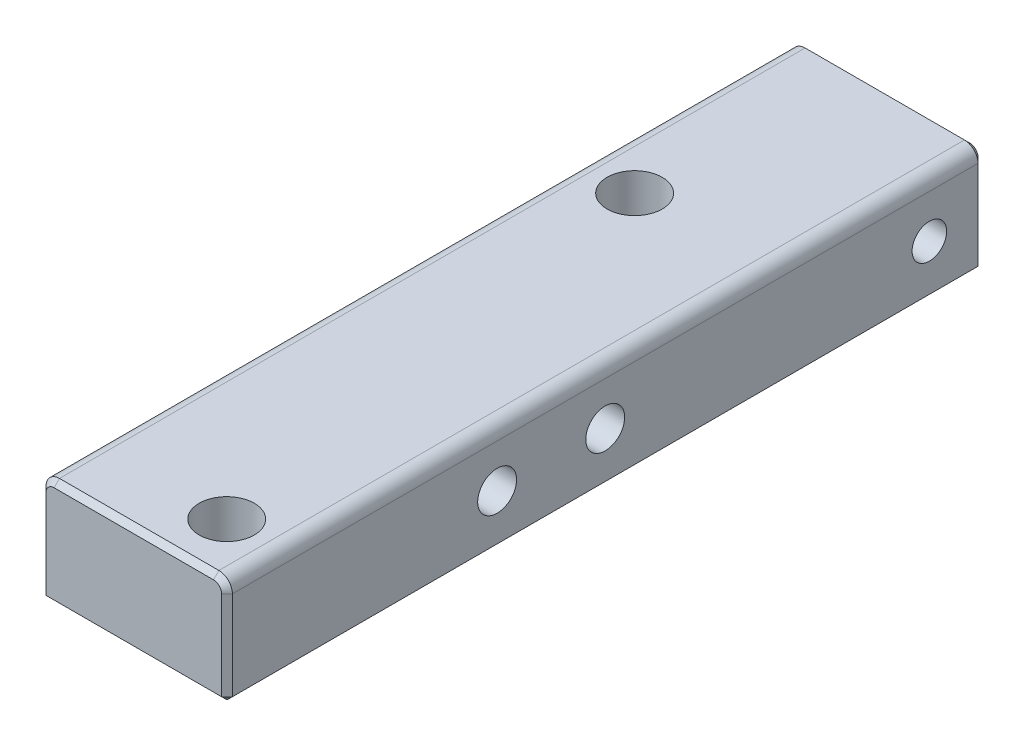
SolidWorks part; units mm, degrees
ref_plane "Front Plane" through (0, 0, 0) normal (0, 0, 1) x (1, 0, 0)
ref_plane "Top Plane" through (0, 0, 0) normal (0, 1, 0) x (1, 0, 0)
ref_plane "Right Plane" through (0, 0, 0) normal (1, 0, 0) x (0, 0, -1)
sketch "Sketch1" plane through (0, 0, 0) normal (0, 0, 1) x (1, 0, 0)
  line L1 (0, 0) -> (21.9075, 0)
  line L2 (0, 0) -> (0, 12.7)
  line L3 (0, 12.7) -> (21.9075, 12.7)
  line L4 (21.9075, 0) -> (21.9075, 12.7)
  dimension "D1" = 21.9075
  dimension "D2" = 12.7
extrude "Boss-Extrude1" add sketch "Sketch1" along normal blind 101.6
fillet "Fillet1" radius 1.5875 2 edges at (21.9075, 12.7, 50.8) (0, 12.7, 50.8)
sketch "Sketch2" plane through (21.9075, 0, 0) normal (1, 0, 0) x (0, 0, -1)
  line L0 (-101.6, 6.0452) -> (0, 6.0452) construction
  line L1 (-101.6, 0) -> (-101.6, 11.1125) construction
  line L2 (0, 0) -> (0, 11.1125) construction
  line L3 (-101.6, 0) -> (0, 0) construction
  circle A4 centre (-57.15, 6.0452) radius 2.286
  circle A11 centre (-44.45, 6.0452) radius 2.286
  circle A12 centre (-6.35, 6.0452) radius 2.032
  dimension "D1" = 6.0452
  dimension "D2" = 4.572
  dimension "D3" = 4.064
  dimension "D6" = 6.35
  dimension "D4" = 12.7
  dimension "D5" = 38.1
extrude "Cut-Extrude2" cut sketch "Sketch2" against normal through all contours A4 L0 | L0 A4 | L0 A11 | A11 L0 | L0 A12 | A12 L0 region at (21.9075, 7.0154, 57.15) region at (21.9075, 6.9076, 6.35) region at (21.9075, 5.1828, 6.35) region at (21.9075, 7.0154, 44.45) region at (21.9075, 5.075, 44.45) region at (21.9075, 5.075, 57.15)
sketch "Sketch3" plane through (0, 0, 0) normal (0, -1, 0) x (1, 0, 0)
  circle A4 centre (15.5575, 82.583) radius 3.2385
  circle A5 centre (6.35, 25.433) radius 3.2385
  point P2 (7.7442, 23.6666)
  dimension "D1" = 6.477
extrude "Cut-Extrude3" cut sketch "Sketch3" along direction (0, -1, 0) on the side against the normal up to next (12.7 mm away) contours A4 | A5 region at (15.5575, 0, 82.583)
sketch "Sketch5" plane through (0, 0, 101.6) normal (0, 0, 1) x (1, 0, 0)
  line L0 (21.9075, 0) -> (21.9075, 11.1125) construction
  line L1 (0, 0) -> (21.9075, 0)
  line L2 (0, 0) -> (0, 15.875)
  line L3 (0, 15.875) -> (21.9075, 15.875)
  line L4 (21.9075, 0) -> (21.9075, 15.875)
  dimension "D1" = 15.875
extrude "Cut-Extrude5" cut sketch "Sketch5" against normal blind 12.7 contours L3 L4 L1 L2
chamfer "Chamfer1" distance 0.635 angle 45 14 edges at (0, 5.5562, 0) (0, 5.5562, 88.9) (0.465, 12.235, 0) (0.465, 12.235, 88.9) (10.9537, 12.7, 0) (10.9537, 12.7, 88.9) (21.4425, 12.235, 0) (21.4425, 12.235, 88.9) (21.9075, 5.5562, 0) (21.9075, 5.5562, 88.9) (10.9537, 0, 0) (0, 0, 44.45) (21.9075, 0, 44.45) (10.9537, 0, 88.9)
ref_plane "Plane1" through (24.4475, 0, 0) normal (1, 0, 0) x (0, 0, -1)
mirror "Mirror3" [suppressed] about plane through (24.4475, 0, 0) normal (1, 0, 0) of bodies 105 108
sketch "Sketch6" plane through (0, 0, 0) normal (0, 0, -1) x (-1, 0, 0)
  line L1 (-21.9761, -0.3556) -> (0.5961, -0.3556)
  line L2 (-21.9761, -0.3556) -> (-21.9761, 13.1218)
  line L3 (-21.9761, 13.1218) -> (0.5961, 13.1218)
  line L4 (0.5961, -0.3556) -> (0.5961, 13.1218)
extrude "Cut-Extrude6" [suppressed] cut sketch "Sketch6" against normal through all both and the other way through all
